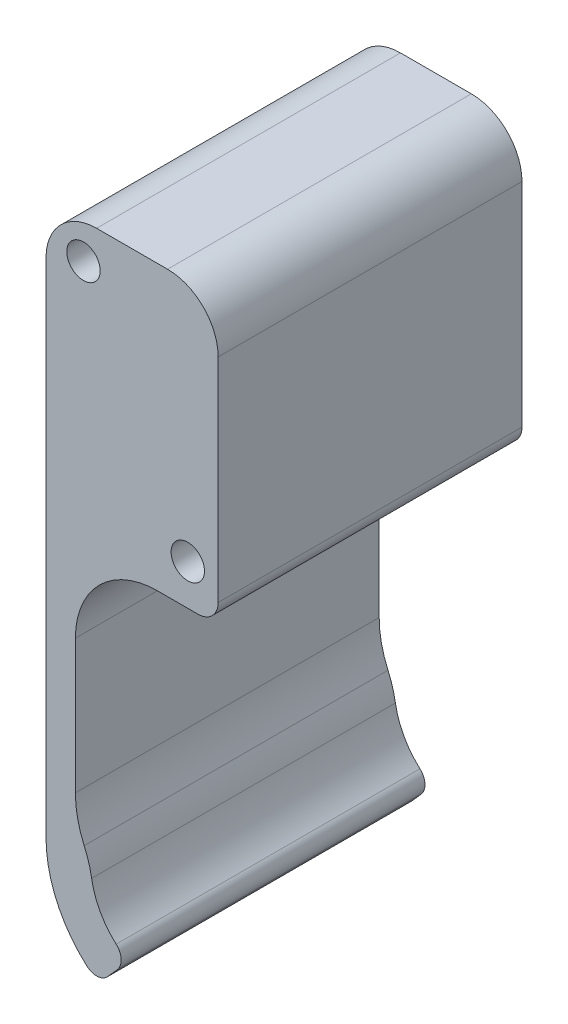
SolidWorks part; units mm, degrees
ref_plane "前视基准面" through (0, 0, 0) normal (0, 0, 1) x (1, 0, 0)
ref_plane "上视基准面" through (0, 0, 0) normal (0, 1, 0) x (1, 0, 0)
ref_plane "右视基准面" through (0, 0, 0) normal (1, 0, 0) x (0, 0, -1)
sketch "草图1" plane through (0, 0, 0) normal (0, 0, 1) x (1, 0, 0)
  line L1 (-10, -17.75) -> (10, -17.75)
  line L2 (-19, -8.75) -> (-19, 9.75)
  line L3 (-11, 17.75) -> (11, 17.75)
  line L4 (19, -8.75) -> (19, 9.75)
  line L5 (-19, -17.75) -> (19, 17.75) construction
  line L6 (-19, 17.75) -> (19, -17.75) construction
  arc A0 (19, -8.75) -> (10, -17.75) centre (10, -8.75) cw
  arc A1 (-10, -17.75) -> (-19, -8.75) centre (-10, -8.75) cw
  arc A2 (19, 9.75) -> (11, 17.75) centre (11, 9.75) ccw
  arc A3 (-19, 9.75) -> (-11, 17.75) centre (-11, 9.75) cw
  point P0 (0, 0)
  dimension "D3" = 9
  dimension "D4" = 8
  dimension "D1" = 35.5
  dimension "D2" = 38
sketch "草图2" plane through (0, 0, 0) normal (0, 0, 1) x (1, 0, 0)
  line L1 (-22, 40.85) -> (-22, -8.75)
  line L5 (0, 0) -> (0, 50000) construction
  line L6 (0, 0) -> (50000, 0) construction
  line L7 (-19, -8.75) -> (-19, 9.75) construction
  line L8 (-22, 45.85) -> (0, 45.85) construction
  line L9 (-5, 77.85) -> (5, 77.85) construction
  line L10 (-5, 77.85) -> (-5, 17.85) construction
  line L11 (-5, 17.85) -> (5, 17.85) construction
  line L12 (5, 77.85) -> (5, 17.85) construction
  line L13 (-5, 77.85) -> (5, 17.85) construction
  line L14 (-5, 17.85) -> (5, 77.85) construction
  line L15 (-10, -17.85) -> (-10, -20.75)
  line L23 (11, 17.85) -> (-11, 17.85)
  line L24 (19.1, -8.75) -> (19.1, 9.75)
  line L25 (-10, -17.85) -> (10, -17.85)
  line L26 (-19.1, 9.75) -> (-19.1, -8.75)
  line L27 (11, 17.85) -> (-11, 17.85) construction
  line L30 (-19.1, 9.75) -> (-19.1, -8.75)
  line L31 (-5, 17.85) -> (-5, 45.85)
  line L32 (-11, 17.85) -> (-5, 17.85)
  line L33 (-17, 45.85) -> (-5, 45.85)
  arc A1 (-17, 45.85) -> (-22, 40.85) centre (-17, 40.85) ccw
  arc A4 (-22, -8.75) -> (-10, -20.75) centre (-10, -8.75) ccw
  arc A8 (19.1, 9.75) -> (11, 17.85) centre (11, 9.75) ccw
  arc A9 (10, -17.85) -> (19.1, -8.75) centre (10, -8.75) ccw
  arc A10 (-19.1, -8.75) -> (-10, -17.85) centre (-10, -8.75) ccw
  arc A11 (-11, 17.85) -> (-19.1, 9.75) centre (-11, 9.75) ccw
  arc A14 (-19.1, -8.75) -> (-10, -17.85) centre (-10, -8.75) ccw
  arc A15 (-11, 17.85) -> (-19.1, 9.75) centre (-11, 9.75) ccw
  point P10 (0, 47.85)
  dimension "D7" = 24
  dimension "D8" = 5
  dimension "D1" = 3
  dimension "D2" = 60
  dimension "D3" = 10
  dimension "D4" = 0.1
  dimension "D5" = 28
  dimension "D6" = 5
extrude "凸台-拉伸1" add sketch "草图2" along normal blind 30
sketch "草图3" plane through (-5, 0, 0) normal (1, 0, 0) x (0, 0, -1)
  line L0 (-15, 28) -> (-15, -49972) construction
  line L1 (-30, 45.85) -> (0, 45.85) construction
  line L3 (-15, 33.35) -> (49985, 33.35) construction
  circle A0 centre (-20, 28.35) radius 1.6
  circle A1 centre (-10, 28.35) radius 1.6
  circle A3 centre (-10, 38.35) radius 1.6
  circle A4 centre (-20, 38.35) radius 1.6
  point P4 (-15, 45.85)
  dimension "D1" = 3.2
  dimension "D4" = 10
  dimension "D2" = 10
  dimension "D3" = 17.5
extrude "切除-拉伸1" [suppressed] cut sketch "草图3" against normal through all
sketch "草图4" plane through (0, 0, 30) normal (0, 0, 1) x (1, 0, 0)
  line L0 (-10, -20.75) -> (-10, -17.85) construction
  line L1 (-10, -17.85) -> (-10, -20.75)
  arc A0 (-17.9621, -17.728) -> (-16.0379, -15.5583) centre (-17, -16.6432) ccw
  arc A1 (-22, -8.75) -> (-10, -20.75) centre (-10, -8.75) ccw construction
  arc A2 (-19.1, -8.75) -> (-10, -17.85) centre (-10, -8.75) ccw construction
  arc A3 (-10, -20.75) -> (-17.9621, -17.728) centre (-10, -8.75) cw
  arc A4 (-10, -17.85) -> (-16.0379, -15.5583) centre (-10, -8.75) cw
  dimension "D1" = 7
  dimension "D3" = 12
  dimension "D5" = 9.1
extrude "切除-拉伸2" cut sketch "草图4" against normal through all
sketch "草图5" plane through (0, 0, 30) normal (0, 0, 1) x (1, 0, 0)
  line L6 (-17.6, -8.75) -> (-19.1, -8.75)
  line L7 (-19.1, -8.75) -> (-19.1, 9.75) construction
  line L8 (-15.9152, -17.6053) -> (-14.953, -16.5203)
  line L10 (-19.1, -8.75) -> (-19.1, -14.5545)
  line L11 (-19.1, -14.5545) -> (-15.9152, -17.6053)
  line L15 (-17.6, -8.75) -> (-17.6, 9.75) construction
  arc A6 (-17.9621, -17.728) -> (-16.0379, -15.5583) centre (-17, -16.6432) ccw construction
  arc A7 (-17.6, -8.75) -> (-15.0738, -14.4083) centre (-10, -8.75) ccw
  arc A8 (-14.953, -16.5203) -> (-15.0738, -14.4083) centre (-16.0752, -15.5251) ccw
  circle A10 centre (-10, -8.75) radius 9.1 construction
  dimension "D1" = 1.5
  dimension "D3" = 18.2
  dimension "D2" = 1.5
extrude "凸台-拉伸2" add sketch "草图5" against normal through all
fillet "圆角2" radius 10 1 edges at (-19.1, -8.75, 15)
fillet "圆角3" radius 10 1 edges at (-17.6, -8.75, 15)
sketch "草图6" plane through (0, 0, 30) normal (0, 0, 1) x (1, 0, 0)
  line L0 (-11, 17.85) -> (-5, 17.85) construction
  line L1 (-5, 17.85) -> (-5, 45.85) construction
  circle A0 centre (-8, 21.85) radius 1.65
  circle A3 centre (-18.3014, 42.3823) radius 1.65
  dimension "D1" = 3.3
  dimension "D4" = 3.3
  dimension "D5" = 10.3014
  dimension "D6" = 20.5323
  dimension "D2" = 4
  dimension "D3" = 3
extrude "切除-拉伸3" cut sketch "草图6" against normal through all
fillet "圆角4" radius 2 1 edges at (-5, 17.85, 15)
fillet "圆角6" radius 5 1 edges at (-5, 45.85, 15)
